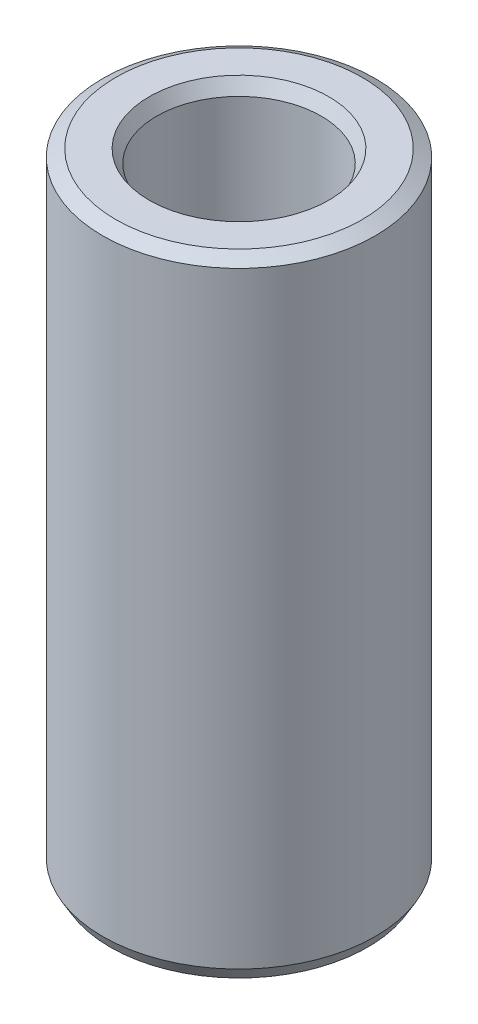
SolidWorks part; units mm, degrees
ref_plane "Front Plane" through (0, 0, 0) normal (0, 0, 1) x (1, 0, 0)
ref_plane "Top Plane" through (0, 0, 0) normal (0, 1, 0) x (1, 0, 0)
ref_plane "Right Plane" through (0, 0, 0) normal (1, 0, 0) x (0, 0, -1)
sketch "Sketch1" plane through (0, 0, 0) normal (0, 1, 0) x (1, 0, 0)
  circle A0 centre (0, 0) radius 50
  dimension "SLEEVE_OD" = 100
extrude "Boss-Extrude1" add sketch "Sketch1" along normal blind 230.1919
sketch "Sketch2" plane through (0, 0, 0) normal (0, 1, 0) x (1, 0, 0)
  circle A0 centre (0, 0) radius 30.1741
  dimension "BORE_D" = 60.3482
extrude "Cut-Extrude1" cut sketch "Sketch2" along normal through all
chamfer "Chamfer1" distance 2.7642 angle 60 4 edges at (0, 230.1919, 30.1741) (0, 0, 30.1741) (0, 0, 50) (0, 230.1919, 50) first distance on face at (0, 230.1919, 30.1741) first distance on face at (0, 0, 30.1741) first distance on face at (0, 230.1919, 50)
